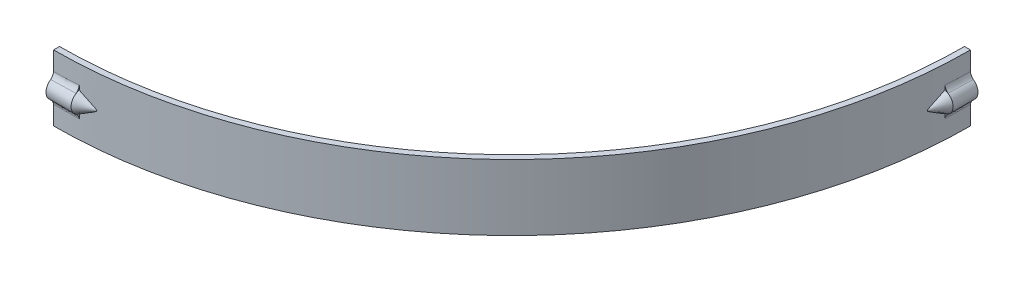
SolidWorks part; units mm, degrees
ref_plane "Front Plane" through (0, 0, 0) normal (0, 0, 1) x (1, 0, 0)
ref_plane "Top Plane" through (0, 0, 0) normal (0, 1, 0) x (1, 0, 0)
ref_plane "Right Plane" through (0, 0, 0) normal (1, 0, 0) x (0, 0, -1)
sketch "Sketch1" plane through (0, 0, 0) normal (0, 0, 1) x (1, 0, 0)
  line L0 (0, 3.3639) -> (0, -36.2756) construction
  line L1 (176.7332, 12.7) -> (174.4472, 12.7)
  line L2 (176.7332, 12.7) -> (176.7332, -12.7)
  line L3 (176.7332, -12.7) -> (174.4472, -12.7)
  line L4 (174.4472, 12.7) -> (174.4472, -12.7)
  line L5 (176.7332, 12.7) -> (174.4472, -12.7) construction
  line L6 (176.7332, -12.7) -> (174.4472, 12.7) construction
  point P0 (175.5902, 0)
  dimension "D1" = 25.4
  dimension "D2" = 2.286
  dimension "D3" = 175.5902
revolve "Revolve1" add sketch "Sketch1" angle 90 about L0
sketch "Sketch4" plane through (0, 0, 0) normal (-1, 0, 0) x (0, 0, 1)
  line L1 (176.7332, 12.7) -> (174.4472, 12.7) construction
  circle A0 centre (175.5902, 0) radius 4.064
  point P5 (175.5902, 12.7)
  dimension "D2" = 8.128
extrude "Boss-Extrude1" add sketch "Sketch4" against normal blind 9.652
sketch "Sketch6" plane through (9.652, 0, 0) normal (1, 0, 0) x (0, 0, -1)
  circle A0 centre (-175.5902, 0) radius 3.175
  circle A2 centre (-175.5902, 0) radius 4.064 construction
  dimension "D1" = 6.35
fillet "Fillet6" radius 2.54 2 edges at (8.128, 3.95, 176.5462) (1.5261, -3.9019, 176.7266) conic radius 5.08
fillet "Fillet8" radius 2.54 2 edges at (8.128, -3.8394, 174.2577) (1.526, 3.898, 174.4405) conic radius 5.08
sketch "Sketch7" plane through (0, 0, 0) normal (0, 0, -1) x (-1, 0, 0)
  line L1 (-176.7332, 12.7) -> (-174.4472, 12.7) construction
  circle A0 centre (-175.5902, 0) radius 4.064
  point P7 (-175.5902, 12.7)
  dimension "D1" = 8.128
extrude "Boss-Extrude2" add sketch "Sketch7" against normal blind 9.6012
sketch "Sketch8" plane through (0, 0, 9.6012) normal (0, 0, 1) x (1, 0, 0)
  circle A0 centre (175.5902, 0) radius 3.175
  circle A1 centre (175.5902, 0) radius 4.064 construction
  dimension "D1" = 6.35
fillet "Fillet11" radius 2.54 4 edges at (174.441, -3.8981, 1.4752) (174.2577, 3.8394, 8.128) (176.5462, -3.95, 8.128) (176.727, 3.9018, 1.4752) conic radius 5.08
sketch "Sketch9" plane through (0, 0, 0) normal (-1, 0, 0) x (0, 0, 1)
  circle A0 centre (175.5902, 0) radius 3.3655
  dimension "D1" = 6.731
extrude "Cut-Extrude1" cut sketch "Sketch9" against normal blind 9.525
sketch "Sketch10" plane through (0, 0, 0) normal (0, 0, -1) x (-1, 0, 0)
  circle A0 centre (-175.5902, 0) radius 3.3655
  dimension "D1" = 6.731
extrude "Cut-Extrude2" cut sketch "Sketch10" against normal blind 9.525
sketch "Sketch11" plane through (0, 0, 0) normal (0, 1, 0) x (1, 0, 0)
  line L0 (9.652, -171.5262) -> (9.652, -175.4632)
  line L1 (9.652, -179.6542) -> (16.4711, -175.7172)
  line L2 (16.4711, -175.4632) -> (9.652, -171.5262)
  line L3 (9.652, -175.5902) -> (13.6215, -175.5902) construction
  line L4 (9.652, -175.4632) -> (16.4711, -175.4632)
  line L5 (16.4711, -175.7172) -> (9.652, -175.7172)
  line L6 (9.652, -175.7172) -> (9.652, -179.6542)
  line L7 (9.652, -178.7652) -> (9.652, -172.4152) construction
  dimension "D1" = 60
  dimension "D2" = 60
  dimension "D3" = 0.254
revolve "Revolve7" add sketch "Sketch11" angle 180 about L3 region at (11.925, 0, 174.1509) region at (11.925, 0, 177.0295)
sketch "Sketch12" plane through (0, 0, 0) normal (0, 1, 0) x (1, 0, 0)
  line L0 (171.5262, -9.6012) -> (175.4632, -16.4203)
  line L1 (175.7172, -16.4203) -> (179.6542, -9.6012)
  line L2 (177.6983, -9.6012) -> (179.6542, -9.6012) construction
  line L3 (179.6542, -9.6012) -> (175.7172, -9.6012)
  line L4 (175.7172, -9.6012) -> (175.7172, -16.4203)
  line L6 (175.4632, -16.4203) -> (175.4632, -9.6012)
  line L7 (175.5902, -9.9069) -> (175.5902, -14.0613) construction
  line L8 (175.4632, -9.6012) -> (171.5262, -9.6012)
  dimension "D1" = 60
  dimension "D2" = 60
  dimension "D3" = 0.254
  dimension "D4" = 0.127
revolve "Revolve8" add sketch "Sketch12" angle 203 about L7 region at (174.1509, 0, 11.8742) region at (177.0295, 0, 11.8742)
